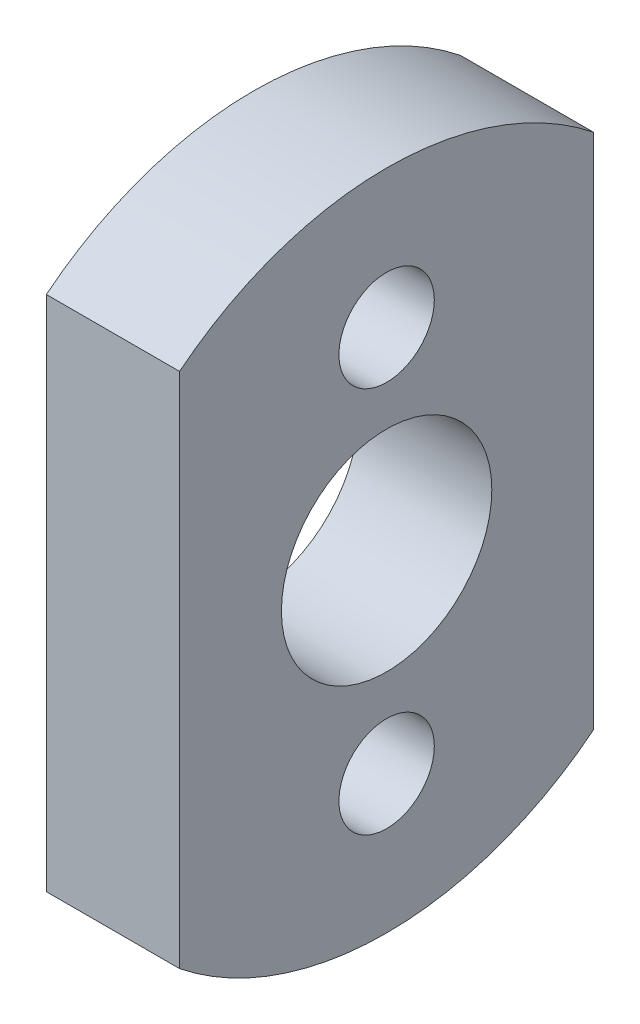
SolidWorks part; units mm, degrees
material "Beech"
ref_plane "Front" through (0, 0, 0) normal (0, 0, 1) x (1, 0, 0)
ref_plane "Top" through (0, 0, 0) normal (0, 1, 0) x (1, 0, 0)
ref_plane "Right" through (0, 0, 0) normal (1, 0, 0) x (0, 0, -1)
ref_axis "side-side" through (80.9, 0, 0) along (-1, 0, 0)
ref_axis "up-down" through (0, 50, 0) along (0, -1, 0)
ref_axis "front-back" through (0, 0, -80.9) along (0, 0, 1)
sketch "Sketch1" plane through (0, 0, 0) normal (1, 0, 0) x (0, 0, -1)
  line L0 (0, 0) -> (-24.1267, 0) construction
  line L1 (-7.5, 9.3675) -> (7.5, -9.3675) construction
  line L2 (-7.5, 9.3675) -> (7.5, 9.3675) construction
  line L3 (-7.5, 9.3675) -> (-7.5, -9.3675)
  line L4 (-7.5, -9.3675) -> (7.5, -9.3675) construction
  line L5 (7.5, 9.3675) -> (7.5, -9.3675)
  circle A0 centre (0, 0) radius 12 construction
  circle A1 centre (0, 7) radius 1.7272
  circle A2 centre (0, -7) radius 1.7272
  circle A3 centre (0, 0) radius 3.81
  arc A4 (-7.5, 9.3675) -> (7.5, 9.3675) centre (0, 0) cw
  arc A5 (-7.5, -9.3675) -> (7.5, -9.3675) centre (0, 0) ccw
  dimension "D1" = 3.4544
  dimension "D2" = 24
  dimension "D3" = 14
  dimension "D4" = 7.62
  dimension "D5" = 15
  dimension "D6" = 18.735
extrude "Boss-Extrude1" add sketch "Sketch1" along normal blind 4.826
